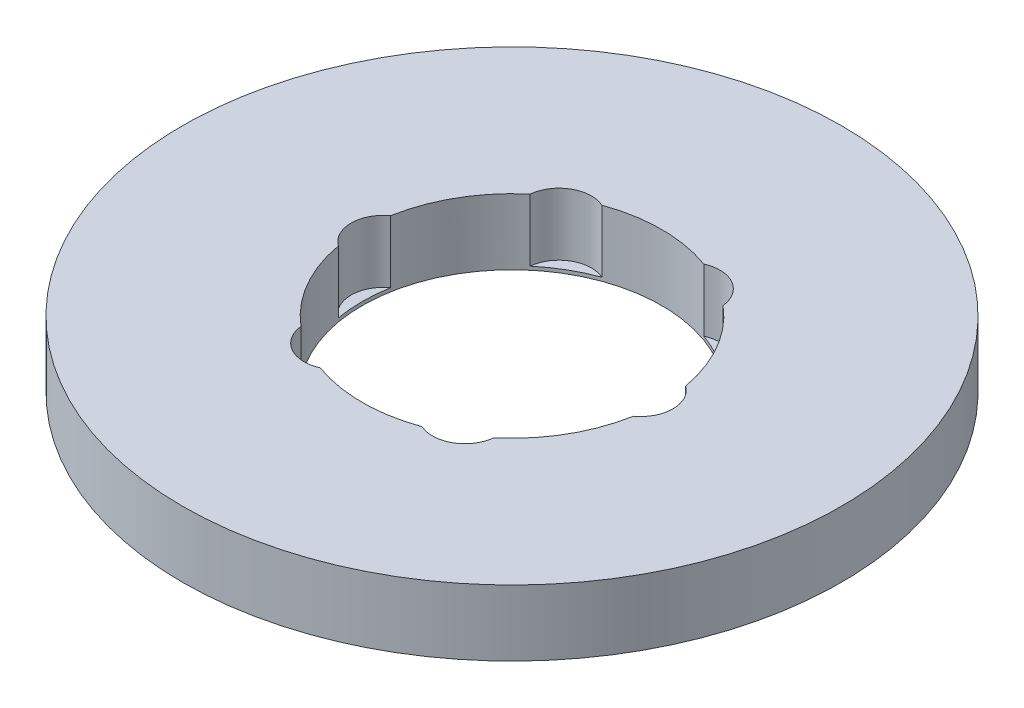
SolidWorks part; units mm, degrees
ref_plane "Front Plane" through (0, 0, 0) normal (0, 0, 1) x (1, 0, 0)
ref_plane "Top Plane" through (0, 0, 0) normal (0, 1, 0) x (1, 0, 0)
ref_plane "Right Plane" through (0, 0, 0) normal (1, 0, 0) x (0, 0, -1)
sketch "Sketch1" plane through (0, 0, 0) normal (0, 1, 0) x (1, 0, 0)
  circle A0 centre (0, 0) radius 55
  dimension "FLANGE_OD" = 110
extrude "Boss-Extrude1" add sketch "Sketch1" along normal blind 11
sketch "Sketch2" plane through (0, 0, 0) normal (0, 1, 0) x (1, 0, 0)
  circle A0 centre (0, 0) radius 25
  dimension "BORE_D" = 50
extrude "Cut-Extrude1" cut sketch "Sketch2" along normal through all
sketch "Sketch3" plane through (0, 11, 0) normal (0, 1, 0) x (1, 0, 0)
  circle A0 centre (0, 0) radius 21.4681 construction
  circle A1 centre (-21.4681, 0) radius 5.3876
  dimension "BOLT_D" = 10.7752
  dimension "BOLT_PCD" = 42.9362
extrude "Cut-Extrude2" cut sketch "Sketch3" against normal blind 10.4127
pattern_circular "CirPattern1" count 6 over 360 about axis through (0, 0, 0) along (0, 1, 0) of "Cut-Extrude2"
